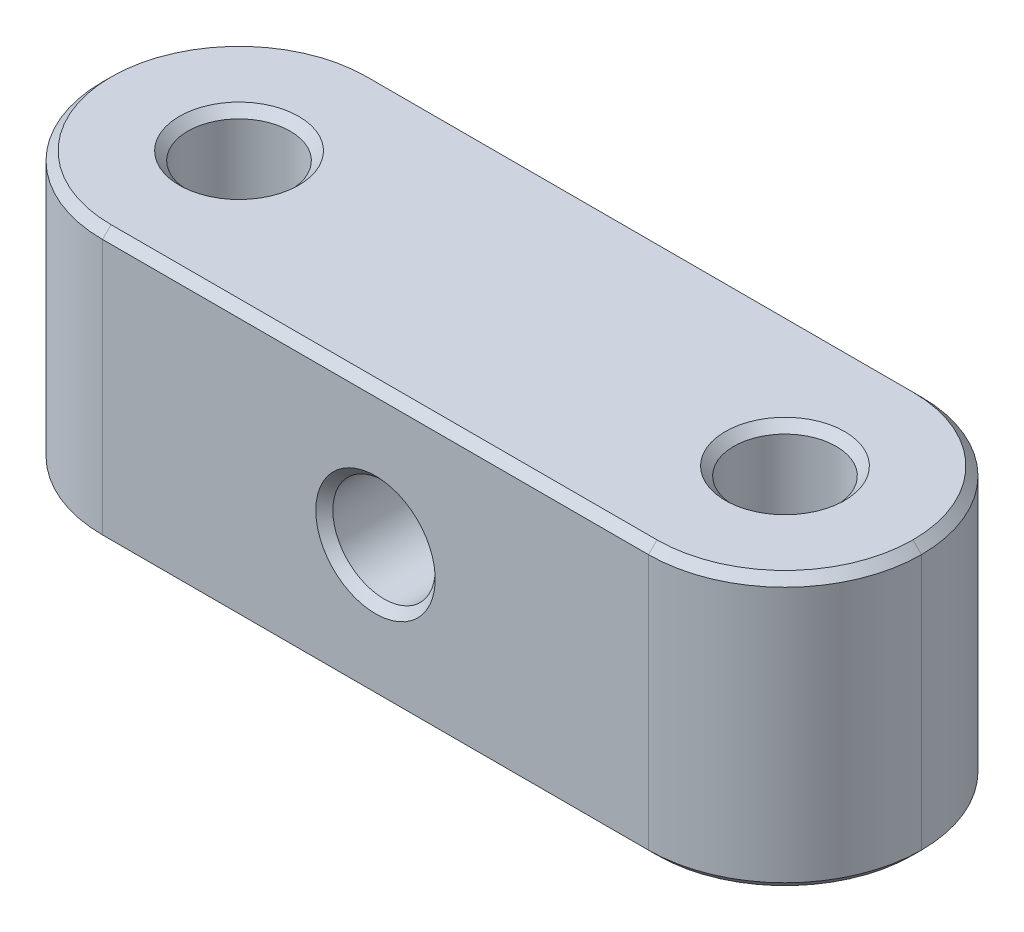
SolidWorks part; units mm, degrees
ref_plane "Front Plane" through (0, 0, 0) normal (0, 0, 1) x (1, 0, 0)
ref_plane "Top Plane" through (0, 0, 0) normal (0, 1, 0) x (1, 0, 0)
ref_plane "Right Plane" through (0, 0, 0) normal (1, 0, 0) x (0, 0, -1)
sketch "Sketch1" plane through (0, 0, 0) normal (0, 1, 0) x (1, 0, 0)
  line L1 (0, 0) -> (38.1, 0)
  line L2 (0, 0) -> (0, 12.7)
  line L3 (0, 12.7) -> (38.1, 12.7)
  line L4 (38.1, 0) -> (38.1, 12.7)
  circle A0 centre (6.35, 6.35) radius 2.3813
  circle A1 centre (31.75, 6.35) radius 2.3812
  dimension "D7" = 4.7625
  dimension "D8" = 4.7625
  dimension "D1" = 38.1
  dimension "D2" = 12.7
  dimension "D3" = 6.35
  dimension "D4" = 6.35
  dimension "D5" = 6.35
  dimension "D6" = 25.4
extrude "Boss-Extrude1" add sketch "Sketch1" along normal blind 12.7
sketch "Sketch2" plane through (0, 0, 0) normal (0, 0, 1) x (1, 0, 0)
  line L0 (0, 12.7) -> (0, 0) construction
  line L1 (0, 0) -> (38.1, 0) construction
  circle A0 centre (19.05, 6.35) radius 2.3813
  dimension "D3" = 4.7625
  dimension "D1" = 19.05
  dimension "D2" = 6.35
extrude "Cut-Extrude1" cut sketch "Sketch2" against normal through all both and the other way through all
fillet "Fillet2" radius 6.35 4 edges at (0, 6.35, -12.7) (0, 6.35, 0) (38.1, 6.35, -12.7) (38.1, 6.35, 0)
chamfer "Chamfer3" distance 0.3969 angle 45 18 edges at (16.6687, 6.35, 0) (21.4313, 6.35, -12.7) (31.75, 0, -3.9688) (19.05, 0, 0) (36.2401, 0, -1.8599) (36.2401, 0, -10.8401) (19.05, 0, -12.7) (1.8599, 0, -10.8401) (1.8599, 0, -1.8599) (6.35, 0, -3.9687) (31.75, 12.7, -3.9688) (6.35, 12.7, -3.9687) (36.2401, 12.7, -10.8401) (36.2401, 12.7, -1.8599) (19.05, 12.7, 0) (1.8599, 12.7, -1.8599) (1.8599, 12.7, -10.8401) (19.05, 12.7, -12.7)
